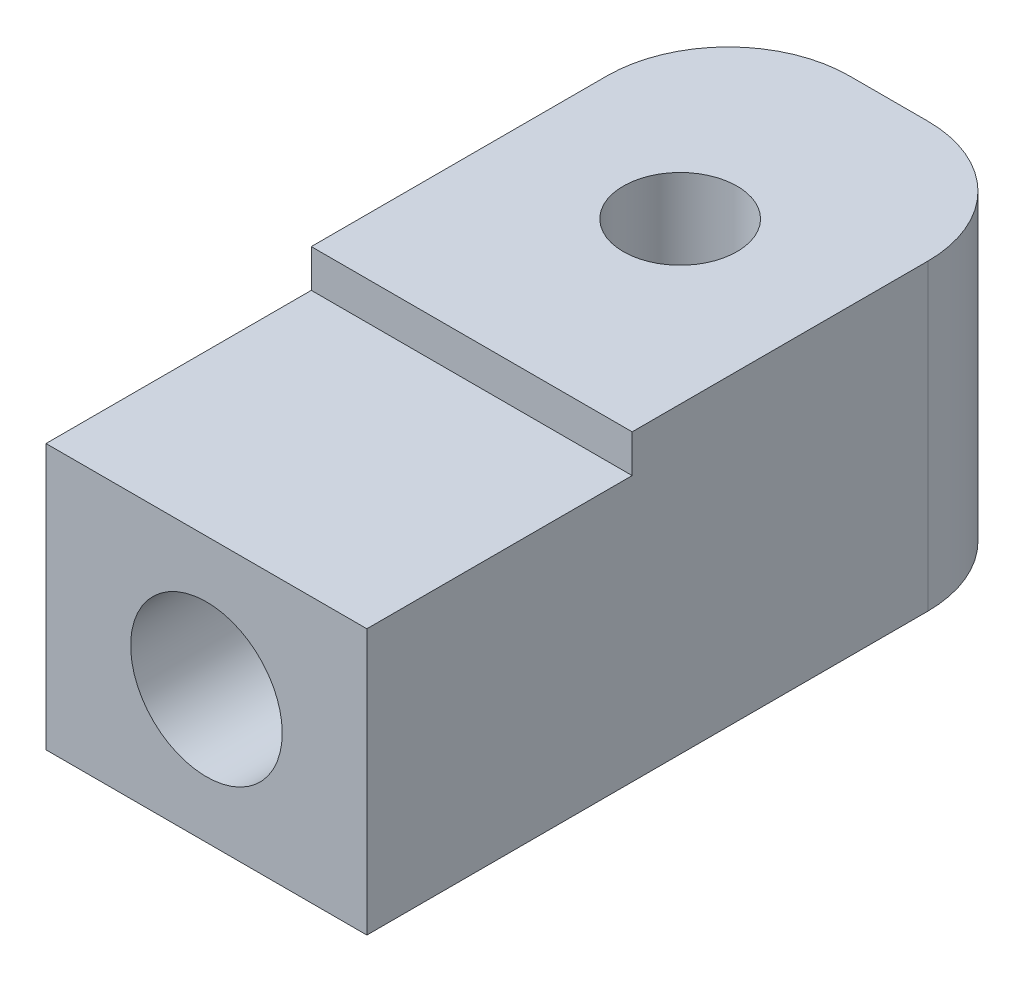
SolidWorks part; units mm, degrees
ref_plane "Front Plane" through (0, 0, 0) normal (0, 0, 1) x (1, 0, 0)
ref_plane "Top Plane" through (0, 0, 0) normal (0, 1, 0) x (1, 0, 0)
ref_plane "Right Plane" through (0, 0, 0) normal (1, 0, 0) x (0, 0, -1)
sketch "Sketch1" plane through (0, 0, 0) normal (0, 1, 0) x (1, 0, 0)
  line L0 (-110.6478, -444.0842) -> (947.6498, -444.0842)
  line L1 (947.6498, -1319.0842) -> (-110.6478, -1319.0842)
  line L2 (947.6498, -1319.0842) -> (947.6498, 930.9158)
  line L3 (947.6498, 930.9158) -> (-110.6478, 930.9158)
  line L4 (-110.6478, -1319.0842) -> (-110.6478, 930.9158)
  line L5 (947.6498, -1319.0842) -> (-110.6478, 930.9158) construction
  line L6 (947.6498, 930.9158) -> (-110.6478, -1319.0842) construction
  point P0 (418.501, -194.0842)
  point P7 (0, 0)
  point P8 (418.501, -194.0842)
  dimension "D1" = 875
extrude "Boss-Extrude4" add sketch "Sketch1" along normal blind 1000 contours L4 L0 L2 L3 region at (418.501, 0, -243.4158)
extrude "Boss-Extrude5" add sketch "Sketch1<7>" along normal blind 875 contours L4 L1 L2 L0 region at (418.501, 0, 881.5842)
sketch "Sketch1<7>" plane through (0, 0, 0) normal (0, 1, 0) x (1, 0, 0) same geometry as "Sketch1"
sketch "Sketch5" plane through (0, 0, 1319.0842) normal (0, 0, 1) x (1, 0, 0)
  line L0 (418.501, 875) -> (418.501, 0) construction
  line L1 (947.6498, 875) -> (-110.6478, 875) construction
  line L2 (947.6498, 0) -> (-110.6478, 0) construction
  circle A0 centre (418.501, 437.5) radius 250
  point P8 (418.501, 437.5)
  point P9 (418.501, 437.5)
extrude "Cut-Extrude1" cut sketch "Sketch5" against normal blind 1188
sketch "Sketch6" plane through (0, 1000, 0) normal (0, 1, 0) x (1, 0, 0)
  line L0 (418.501, 930.9158) -> (418.501, -444.0842) construction
  line L1 (947.6498, 930.9158) -> (-110.6478, 930.9158) construction
  line L2 (-110.6478, -444.0842) -> (947.6498, -444.0842) construction
  circle A1 centre (418.501, 243.4158) radius 187.5
extrude "Cut-Extrude7" cut sketch "Sketch6" against normal blind 875 contours A1
sketch "Sketch7" plane through (0, 0, 0) normal (0, -1, 0) x (-1, 0, 0)
  circle A0 centre (-418.501, 243.4158) radius 237.5
  point P2 (-415.9463, 287.7354)
  point P3 (0, 0)
  point P4 (-418.501, 243.4158)
extrude "Cut-Extrude8" cut sketch "Sketch7" against normal blind 125 contours A0
fillet "Fillet2" radius 400 2 edges at (-110.6478, 500, -930.9158) (947.6498, 500, -930.9158)
